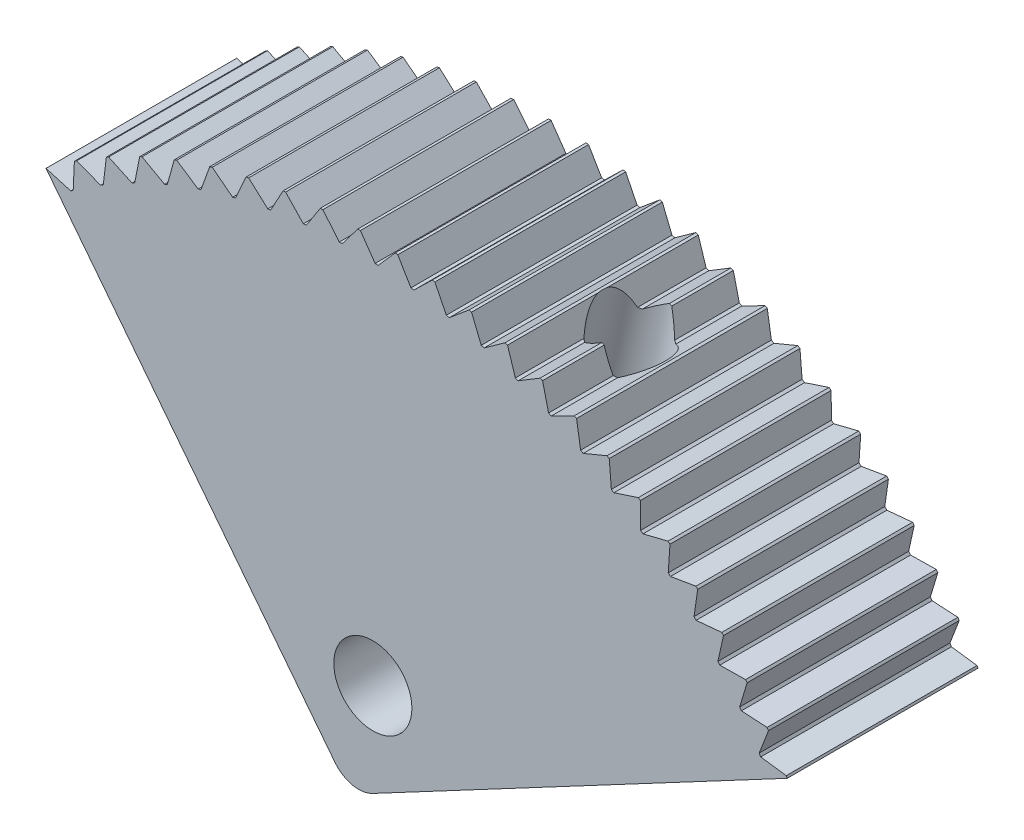
SolidWorks part; units mm, degrees
ref_plane "Front Plane" through (0, 0, 0) normal (0, 0, 1) x (1, 0, 0)
ref_plane "Top Plane" through (0, 0, 0) normal (0, 1, 0) x (1, 0, 0)
ref_plane "Right Plane" through (0, 0, 0) normal (1, 0, 0) x (0, 0, -1)
sketch "Sketch1" plane through (0, 0, 0) normal (0, 0, 1) x (1, 0, 0)
  line L0 (-19.3519, 11.1217) -> (-9.7322, -1.1933)
  line L1 (-8.4748, -1.4607) -> (5.3236, 5.8744)
  line L3 (-24.7927, 18.2415) -> (14.9145, 9.7978) construction
  line L4 (-17.4316, 8.6632) -> (2.569, 4.4101) construction
  line L44 (-9.1521, -1.5558) -> (-7.754, 5.0189) construction
  arc A0 (-19.3519, 11.1217) -> (5.3236, 5.8744) centre (-9.2446, -1.9906) cw
  arc A21 (-8.4748, -1.4607) -> (-9.7322, -1.1933) centre (-8.9441, -0.5777) cw
  circle A22 centre (-8.4713, 1.646) radius 1.3
  point P65 (-9.2952, -2.2794)
  dimension "D3" = 1
  dimension "D6" = 3.2735
  dimension "D2" = 40
  dimension "D1" = 100
  dimension "D4" = 3.1196
  dimension "D5" = 5
extrude "Boss-Extrude1" add sketch "Sketch1" along normal blind 3.175 and the other way blind 3.175
sketch "Sketch2" plane through (0, 0, 0) normal (0, 0, 1) x (1, 0, 0)
  line L0 (-17.4316, 8.6632) -> (2.569, 4.4101) construction
  line L1 (-16.0214, 6.858) -> (3.4265, 2.7224)
  line L2 (-19.3519, 11.1217) -> (-9.7322, -1.1933) construction
ref_plane "Plane1" through (2.6386, 12.4083, 0) normal (-0.208, -0.9781, 0) x (0.9781, -0.208, 0)
sketch "Sketch4" plane through (-6.6231, -5.1736, 0) normal (-0.7881, -0.6156, 0) x (0, 0, 1)
  line L2 (0, 15.2671) -> (0, 0.0361) construction
  line L3 (0, 15.2671) -> (0, 0.0361) construction
  circle A0 centre (0, 15.2671) radius 0.75
  dimension "D1" = 1.5
sweep "Cut-Sweep1" cut profiles "Sketch4" path "Sketch2"
sketch "Sketch3" plane through (2.6386, 12.4083, 0) normal (-0.208, -0.9781, 0) x (0.9781, -0.208, 0)
  line L2 (-7.8364, -0.625) -> (-3.43, -0.625) construction
  line L4 (-5.6332, 0) -> (-5.6332, -0.625) construction
  circle A0 centre (-5.6332, 0) radius 1.1303
  point P6 (-5.6332, -0.625)
  dimension "D1" = 2.2606
extrude "Cut-Extrude2" cut sketch "Sketch3" along normal blind 7.5 and the other way blind 10
sketch "Sketch5" plane through (0, 0, 0) normal (0, 0, 1) x (1, 0, 0)
  line L0 (-18.336, 11.8455) -> (-17.5323, 11.5456)
  line L2 (-19.3519, 11.1217) -> (-18.528, 10.8832)
  line L3 (-18.528, 10.8832) -> (-18.4467, 10.9414)
  line L4 (-18.4467, 10.9414) -> (-18.4074, 11.7983)
  line L5 (-19.3519, 11.1217) -> (-18.4074, 11.7983) construction
  line L6 (-18.8797, 11.46) -> (-18.4873, 10.9123) construction
  line L7 (-17.5323, 11.5456) -> (-17.4469, 11.5976)
  line L8 (-17.4469, 11.5976) -> (-17.3431, 12.4491)
  line L9 (-18.336, 11.8455) -> (-17.3431, 12.4491) construction
  line L10 (-17.8395, 12.1473) -> (-17.4896, 11.5716) construction
  line L11 (-17.2684, 12.4907) -> (-16.4896, 12.1312)
  line L12 (-16.4896, 12.1312) -> (-16.4004, 12.1766)
  line L13 (-16.4004, 12.1766) -> (-16.2329, 13.0179)
  line L14 (-17.2684, 12.4907) -> (-16.2329, 13.0179) construction
  line L15 (-16.7506, 12.7543) -> (-16.445, 12.1539) construction
  line L16 (-16.1552, 13.0538) -> (-15.4057, 12.6367)
  line L17 (-15.4057, 12.6367) -> (-15.3134, 12.6752)
  line L18 (-15.3134, 12.6752) -> (-15.083, 13.5014)
  line L19 (-16.1552, 13.0538) -> (-15.083, 13.5014) construction
  line L20 (-15.6191, 13.2776) -> (-15.3595, 12.6559) construction
  line L21 (-15.0028, 13.5314) -> (-14.2868, 13.059)
  line L22 (-14.2868, 13.059) -> (-14.1919, 13.0905)
  line L23 (-14.1919, 13.0905) -> (-13.8999, 13.8971)
  line L24 (-15.0028, 13.5314) -> (-13.8999, 13.8971) construction
  line L25 (-14.4514, 13.7142) -> (-14.2394, 13.0748) construction
  line L26 (-13.8177, 13.9209) -> (-13.1393, 13.396)
  line L27 (-13.1393, 13.396) -> (-13.0423, 13.4202)
  line L28 (-13.0423, 13.4202) -> (-12.6904, 14.2025)
  line L29 (-13.8177, 13.9209) -> (-12.6904, 14.2025) construction
  line L30 (-13.2541, 14.0617) -> (-13.0908, 13.4081) construction
  line L31 (-12.6067, 14.2201) -> (-11.9698, 13.6455)
  line L32 (-11.9698, 13.6455) -> (-11.8712, 13.6624)
  line L33 (-11.8712, 13.6624) -> (-11.4614, 14.416)
  line L34 (-12.6067, 14.2201) -> (-11.4614, 14.416) construction
  line L35 (-12.034, 14.318) -> (-11.9205, 13.654) construction
  line L36 (-11.3766, 14.4272) -> (-10.7847, 13.8064)
  line L37 (-10.7847, 13.8064) -> (-10.6851, 13.8157)
  line L38 (-10.6851, 13.8157) -> (-10.2198, 14.5363)
  line L39 (-11.3766, 14.4272) -> (-10.2198, 14.5363) construction
  line L40 (-10.7982, 14.4818) -> (-10.7349, 13.811) construction
  line L41 (-10.1343, 14.5411) -> (-9.5909, 13.8775)
  line L42 (-9.5909, 13.8775) -> (-9.4909, 13.8793)
  line L43 (-9.4909, 13.8793) -> (-8.9726, 14.5628)
  line L44 (-10.1343, 14.5411) -> (-8.9726, 14.5628) construction
  line L45 (-9.5535, 14.552) -> (-9.5409, 13.8784) construction
  line L46 (-8.887, 14.5612) -> (-8.3951, 13.8585)
  line L47 (-8.3951, 13.8585) -> (-8.2953, 13.8528)
  line L48 (-8.2953, 13.8528) -> (-7.727, 14.4953)
  line L49 (-8.887, 14.5612) -> (-7.727, 14.4953) construction
  line L50 (-8.307, 14.5283) -> (-8.3452, 13.8557) construction
  line L51 (-7.6418, 14.4873) -> (-7.2042, 13.7495)
  line L52 (-7.2042, 13.7495) -> (-7.105, 13.7364)
  line L53 (-7.105, 13.7364) -> (-6.49, 14.3343)
  line L54 (-7.6418, 14.4873) -> (-6.49, 14.3343) construction
  line L55 (-7.0659, 14.4108) -> (-7.1546, 13.743) construction
  line L56 (-6.4056, 14.3198) -> (-6.0248, 13.5512)
  line L57 (-6.0248, 13.5512) -> (-5.9269, 13.5306)
  line L58 (-5.9269, 13.5306) -> (-5.2686, 14.0805)
  line L59 (-6.4056, 14.3198) -> (-5.2686, 14.0805) construction
  line L60 (-5.8371, 14.2002) -> (-5.9759, 13.5409) construction
  line L61 (-5.1856, 14.0598) -> (-4.8637, 13.2647)
  line L62 (-4.8637, 13.2647) -> (-4.7677, 13.2368)
  line L63 (-4.7677, 13.2368) -> (-4.0698, 13.7355)
  line L64 (-5.1856, 14.0598) -> (-4.0698, 13.7355) construction
  line L65 (-4.6277, 13.8976) -> (-4.8157, 13.2507) construction
  line L66 (-3.9886, 13.7086) -> (-3.7275, 12.8915)
  line L67 (-3.7275, 12.8915) -> (-3.6338, 12.8564)
  line L68 (-3.6338, 12.8564) -> (-2.9004, 13.3013)
  line L69 (-3.9886, 13.7086) -> (-2.9004, 13.3013) construction
  line L70 (-3.4445, 13.5049) -> (-3.6807, 12.874) construction
  line L71 (-2.8214, 13.2683) -> (-2.6226, 12.4338)
  line L72 (-2.6226, 12.4338) -> (-2.5318, 12.3918)
  line L73 (-2.5318, 12.3918) -> (-1.767, 12.7802)
  line L74 (-2.8214, 13.2683) -> (-1.767, 12.7802) construction
  line L75 (-2.2942, 13.0242) -> (-2.5772, 12.4128) construction
  line L76 (-1.6907, 12.7413) -> (-1.5553, 11.8943)
  line L77 (-1.5553, 11.8943) -> (-1.468, 11.8456)
  line L78 (-1.468, 11.8456) -> (-0.6761, 12.1752)
  line L79 (-1.6907, 12.7413) -> (-0.6761, 12.1752) construction
  line L80 (-1.1834, 12.4583) -> (-1.5116, 11.8699) construction
  line L81 (-0.6029, 12.1307) -> (-0.5317, 11.2759)
  line L82 (-0.5317, 11.2759) -> (-0.4482, 11.2208)
  line L83 (-0.4482, 11.2208) -> (0.3662, 11.4898)
  line L84 (-0.6029, 12.1307) -> (0.3662, 11.4898) construction
  line L85 (-0.1184, 11.8103) -> (-0.49, 11.2483) construction
  line L86 (0.4358, 11.44) -> (0.4425, 10.5822)
  line L87 (0.4425, 10.5822) -> (0.5215, 10.5209)
  line L88 (0.5215, 10.5209) -> (1.354, 10.7279)
  line L89 (0.4358, 11.44) -> (1.354, 10.7279) construction
  line L90 (0.8949, 11.0839) -> (0.482, 10.5516) construction
  line L91 (1.4196, 10.6729) -> (1.3617, 9.8171)
  line L92 (1.3617, 9.8171) -> (1.4359, 9.7501)
  line L93 (1.4359, 9.7501) -> (2.2815, 9.8938)
  line L94 (1.4196, 10.6729) -> (2.2815, 9.8938) construction
  line L95 (1.8505, 10.2834) -> (1.3988, 9.7836) construction
  line L96 (2.3428, 9.834) -> (2.2206, 8.985)
  line L97 (2.2206, 8.985) -> (2.2896, 8.9125)
  line L98 (2.2896, 8.9125) -> (3.1436, 8.9922)
  line L99 (2.3428, 9.834) -> (3.1436, 8.9922) construction
  line L100 (2.7432, 9.4131) -> (2.2551, 8.9488) construction
  line L101 (3.2003, 8.928) -> (3.0145, 8.0906)
  line L102 (3.0145, 8.0906) -> (3.0778, 8.0131)
  line L103 (3.0778, 8.0131) -> (3.9354, 8.0282)
  line L104 (3.2003, 8.928) -> (3.9354, 8.0282) construction
  line L105 (3.5678, 8.4781) -> (3.0462, 8.0518) construction
  line L106 (3.987, 7.96) -> (3.7388, 7.1389)
  line L107 (3.7388, 7.1389) -> (3.796, 7.0569)
  line L108 (3.796, 7.0569) -> (4.6524, 7.0074)
  line L109 (3.987, 7.96) -> (4.6524, 7.0074) construction
  line L110 (4.3197, 7.4837) -> (3.7674, 7.0979) construction
  line L111 (4.6987, 6.9354) -> (4.3893, 6.1354)
  line L112 (4.3893, 6.1354) -> (4.4403, 6.0493)
  line L113 (4.4403, 6.0493) -> (5.2904, 5.9355)
  line L114 (4.6987, 6.9354) -> (5.2904, 5.9355) construction
  line L115 (4.9946, 6.4355) -> (4.4148, 6.0924) construction
  arc A0 (3.9354, 8.0282) -> (3.2003, 8.928) centre (-9.2446, -1.9906) ccw
  arc A1 (5.3236, 5.8744) -> (-19.3519, 11.1217) centre (-9.2446, -1.9906) ccw construction
  arc A2 (5.2904, 5.9355) -> (4.6987, 6.9354) centre (-9.2446, -1.9906) ccw
  arc A3 (-18.4074, 11.7983) -> (-19.3519, 11.1217) centre (-9.2446, -1.9906) ccw
  arc A4 (-17.3431, 12.4491) -> (-18.336, 11.8455) centre (-9.2446, -1.9906) ccw
  arc A5 (-16.2329, 13.0179) -> (-17.2684, 12.4907) centre (-9.2446, -1.9906) ccw
  arc A6 (-13.8999, 13.8971) -> (-15.0028, 13.5314) centre (-9.2446, -1.9906) ccw
  arc A7 (-12.6904, 14.2025) -> (-13.8177, 13.9209) centre (-9.2446, -1.9906) ccw
  arc A8 (-11.4614, 14.416) -> (-12.6067, 14.2201) centre (-9.2446, -1.9906) ccw
  arc A9 (-10.2198, 14.5363) -> (-11.3766, 14.4272) centre (-9.2446, -1.9906) ccw
  arc A10 (-8.9726, 14.5628) -> (-10.1343, 14.5411) centre (-9.2446, -1.9906) ccw
  arc A11 (-7.727, 14.4953) -> (-8.887, 14.5612) centre (-9.2446, -1.9906) ccw
  arc A12 (-6.49, 14.3343) -> (-7.6418, 14.4873) centre (-9.2446, -1.9906) ccw
  arc A13 (-5.2686, 14.0805) -> (-6.4056, 14.3198) centre (-9.2446, -1.9906) ccw
  arc A14 (-4.0698, 13.7355) -> (-5.1856, 14.0598) centre (-9.2446, -1.9906) ccw
  arc A15 (-2.9004, 13.3013) -> (-3.9886, 13.7086) centre (-9.2446, -1.9906) ccw
  arc A16 (-1.767, 12.7802) -> (-2.8214, 13.2683) centre (-9.2446, -1.9906) ccw
  arc A17 (-0.6761, 12.1752) -> (-1.6907, 12.7413) centre (-9.2446, -1.9906) ccw
  arc A18 (0.3662, 11.4898) -> (-0.6029, 12.1307) centre (-9.2446, -1.9906) ccw
  arc A19 (1.354, 10.7279) -> (0.4358, 11.44) centre (-9.2446, -1.9906) ccw
  arc A20 (2.2815, 9.8938) -> (1.4196, 10.6729) centre (-9.2446, -1.9906) ccw
  arc A21 (3.1436, 8.9922) -> (2.3428, 9.834) centre (-9.2446, -1.9906) ccw
  arc A22 (4.6524, 7.0074) -> (3.987, 7.96) centre (-9.2446, -1.9906) ccw
  arc A23 (-15.083, 13.5014) -> (-16.1552, 13.0538) centre (-9.2446, -1.9906) ccw
  point P6 (-18.4873, 10.9123)
  point P9 (-18.8797, 11.46)
  point P16 (-17.4896, 11.5716)
  point P19 (-17.8395, 12.1473)
  point P24 (-16.445, 12.1539)
  point P27 (-16.7506, 12.7543)
  point P32 (-15.3595, 12.6559)
  point P35 (-15.6191, 13.2776)
  point P40 (-14.2394, 13.0748)
  point P43 (-14.4514, 13.7142)
  point P48 (-13.0908, 13.4081)
  point P51 (-13.2541, 14.0617)
  point P56 (-11.9205, 13.654)
  point P59 (-12.034, 14.318)
  point P64 (-10.7349, 13.811)
  point P67 (-10.7982, 14.4818)
  point P72 (-9.5409, 13.8784)
  point P75 (-9.5535, 14.552)
  point P80 (-8.3452, 13.8557)
  point P83 (-8.307, 14.5283)
  point P88 (-7.1546, 13.743)
  point P91 (-9.0366, -1.0125)
  point P92 (-7.0659, 14.4108)
  point P97 (-5.9759, 13.5409)
  point P100 (-5.8371, 14.2002)
  point P105 (-4.8157, 13.2507)
  point P108 (-4.6277, 13.8976)
  point P113 (-3.6807, 12.874)
  point P116 (-3.4445, 13.5049)
  point P121 (-2.5772, 12.4128)
  point P124 (-2.2942, 13.0242)
  point P129 (-1.5116, 11.8699)
  point P132 (-1.1834, 12.4583)
  point P137 (-0.49, 11.2483)
  point P140 (-0.1184, 11.8103)
  point P145 (0.482, 10.5516)
  point P148 (0.8949, 11.0839)
  point P153 (1.3988, 9.7836)
  point P156 (1.8505, 10.2834)
  point P161 (2.2551, 8.9488)
  point P164 (2.7432, 9.4131)
  point P169 (3.0462, 8.0518)
  point P172 (3.5678, 8.4781)
  point P177 (3.7674, 7.0979)
  point P180 (4.3197, 7.4837)
  point P185 (4.4148, 6.0924)
  point P188 (4.9946, 6.4355)
  point P191 (-9.2446, -1.9906)
  dimension "D1" = 23
  dimension "D3" = 0.1
  dimension "D4" = 0.6737
  dimension "D5" = 128.243
extrude "Cut-Extrude3" cut sketch "Sketch5" against normal blind 10 and the other way blind 10
